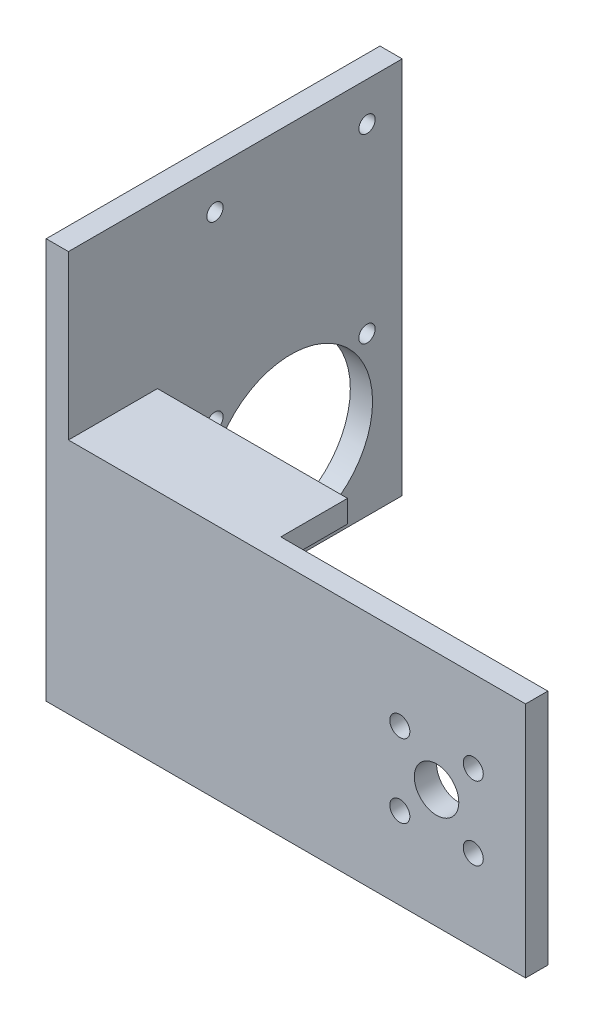
SolidWorks part; units mm, degrees
ref_plane "Front Plane" through (0, 0, 0) normal (0, 0, 1) x (1, 0, 0)
ref_plane "Top Plane" through (0, 0, 0) normal (0, 1, 0) x (1, 0, 0)
ref_plane "Right Plane" through (0, 0, 0) normal (1, 0, 0) x (0, 0, -1)
ref_plane "PZ_p27_000" through (0, 0, 27) normal (0, 0, 1) x (1, 0, 0)
sketch "S_box1" plane through (0, 0, 27) normal (0, 0, 1) x (1, 0, 0)
  line L0 (-52.625, -16) -> (12, -16)
  line L1 (12, -16) -> (12, 16)
  line L2 (12, 16) -> (-52.625, 16)
  line L3 (-52.625, 16) -> (-52.625, -16)
  dimension "P1" = 52.625
  dimension "P2" = 16
  dimension "P3" = 12
  dimension "P4" = 16
  dimension "P5" = 12
  dimension "P6" = 16
  dimension "P7" = 52.625
  dimension "P8" = 16
extrude "Boss_1" add sketch "S_box1" along normal blind 3
ref_plane "PZ_m15_000" through (0, 0, -15) normal (0, 0, 1) x (1, 0, 0)
sketch "S_box2" plane through (0, 0, -15) normal (0, 0, 1) x (1, 0, 0)
  line L0 (-52.625, -13) -> (-49.625, -13)
  line L1 (-49.625, -13) -> (-49.625, 38)
  line L2 (-49.625, 38) -> (-52.625, 38)
  line L3 (-52.625, 38) -> (-52.625, -13)
  dimension "P1" = 52.625
  dimension "P2" = 13
  dimension "P3" = 49.625
  dimension "P4" = 13
  dimension "P5" = 49.625
  dimension "P6" = 38
  dimension "P7" = 52.625
  dimension "P8" = 38
extrude "Boss_2" add sketch "S_box2" along normal blind 45
ref_plane "PZ_p18_000" through (0, 0, 18) normal (0, 0, 1) x (1, 0, 0)
sketch "S_box3" plane through (0, 0, 18) normal (0, 0, 1) x (1, 0, 0)
  line L0 (-50.125, -13.5) -> (-24, -13.5)
  line L1 (-24, -13.5) -> (-24, -10.5)
  line L2 (-24, -10.5) -> (-50.125, -10.5)
  line L3 (-50.125, -10.5) -> (-50.125, -13.5)
  dimension "P1" = 50.125
  dimension "P2" = 13.5
  dimension "P3" = 24
  dimension "P4" = 13.5
  dimension "P5" = 24
  dimension "P6" = 10.5
  dimension "P7" = 50.125
  dimension "P8" = 10.5
extrude "Boss_3" add sketch "S_box3" along normal blind 11.5
sketch "S_box4" plane through (0, 0, 18) normal (0, 0, 1) x (1, 0, 0)
  line L0 (-50.125, 13) -> (-24, 13)
  line L1 (-24, 13) -> (-24, 16)
  line L2 (-24, 16) -> (-50.125, 16)
  line L3 (-50.125, 16) -> (-50.125, 13)
  dimension "P1" = 50.125
  dimension "P2" = 13
  dimension "P3" = 24
  dimension "P4" = 13
  dimension "P5" = 24
  dimension "P6" = 16
  dimension "P7" = 50.125
  dimension "P8" = 16
extrude "Boss_4" add sketch "S_box4" along normal blind 11.5
ref_plane "PZ_p26_900" through (0, 0, 26.9) normal (0, 0, 1) x (1, 0, 0)
sketch "S_hole5" plane through (0, 0, 26.9) normal (0, 0, 1) x (1, 0, 0)
  circle A0 centre (0, 0) radius 3
  dimension "D1_S_hole5" = 6
extrude "Hole_5" cut sketch "S_hole5" along normal blind 3.2
sketch "S_hole6" plane through (0, 0, 26.9) normal (0, 0, 1) x (1, 0, 0)
  circle A0 centre (4.9497, -4.9497) radius 1.35
  dimension "D1_S_hole6" = 2.7
  dimension "P2" = 4.9497
  dimension "P3" = 4.9497
extrude "Hole_6" cut sketch "S_hole6" along normal blind 3.2
sketch "S_hole7" plane through (0, 0, 26.9) normal (0, 0, 1) x (1, 0, 0)
  circle A0 centre (-4.9497, -4.9497) radius 1.35
  dimension "D1_S_hole7" = 2.7
  dimension "P2" = 4.9497
  dimension "P3" = 4.9497
extrude "Hole_7" cut sketch "S_hole7" along normal blind 3.2
sketch "S_hole8" plane through (0, 0, 26.9) normal (0, 0, 1) x (1, 0, 0)
  circle A0 centre (-4.9497, 4.9497) radius 1.35
  dimension "D1_S_hole8" = 2.7
  dimension "P2" = 4.9497
  dimension "P3" = 4.9497
extrude "Hole_8" cut sketch "S_hole8" along normal blind 3.2
sketch "S_hole9" plane through (0, 0, 26.9) normal (0, 0, 1) x (1, 0, 0)
  circle A0 centre (4.9497, 4.9497) radius 1.35
  dimension "D1_S_hole9" = 2.7
  dimension "P2" = 4.9497
  dimension "P3" = 4.9497
extrude "Hole_9" cut sketch "S_hole9" along normal blind 3.2
ref_plane "PX_m52_725" through (-52.725, 0, 0) normal (1, 0, 0) x (0, 0, -1)
sketch "S_hole10" plane through (-52.725, 0, 0) normal (1, 0, 0) x (0, 0, -1)
  circle A0 centre (0, 0) radius 11
  dimension "D1_S_hole10" = 22
extrude "Hole_10" cut sketch "S_hole10" along normal blind 3.2
sketch "S_hole11" plane through (-52.725, 0, 0) normal (1, 0, 0) x (0, 0, -1)
  circle A0 centre (10.25, 8.3) radius 1.1
  dimension "D1_S_hole11" = 2.2
  dimension "P2" = 10.25
  dimension "P3" = 8.3
extrude "Hole_11" cut sketch "S_hole11" along normal blind 3.2
sketch "S_hole12" plane through (-52.725, 0, 0) normal (1, 0, 0) x (0, 0, -1)
  circle A0 centre (-10.25, 8.3) radius 1.1
  dimension "D1_S_hole12" = 2.2
  dimension "P2" = 10.25
  dimension "P3" = 8.3
extrude "Hole_12" cut sketch "S_hole12" along normal blind 3.2
sketch "S_hole13" plane through (-52.725, 0, 0) normal (1, 0, 0) x (0, 0, -1)
  circle A0 centre (10.25, 32.75) radius 1.1
  dimension "D1_S_hole13" = 2.2
  dimension "P2" = 10.25
  dimension "P3" = 32.75
extrude "Hole_13" cut sketch "S_hole13" along normal blind 3.2
sketch "S_hole14" plane through (-52.725, 0, 0) normal (1, 0, 0) x (0, 0, -1)
  circle A0 centre (-10.25, 32.75) radius 1.1
  dimension "D1_S_hole14" = 2.2
  dimension "P2" = 10.25
  dimension "P3" = 32.75
extrude "Hole_14" cut sketch "S_hole14" along normal blind 3.2
equation "\"plate_t\" = 3"
equation "\"clearance\" = 0.4"
